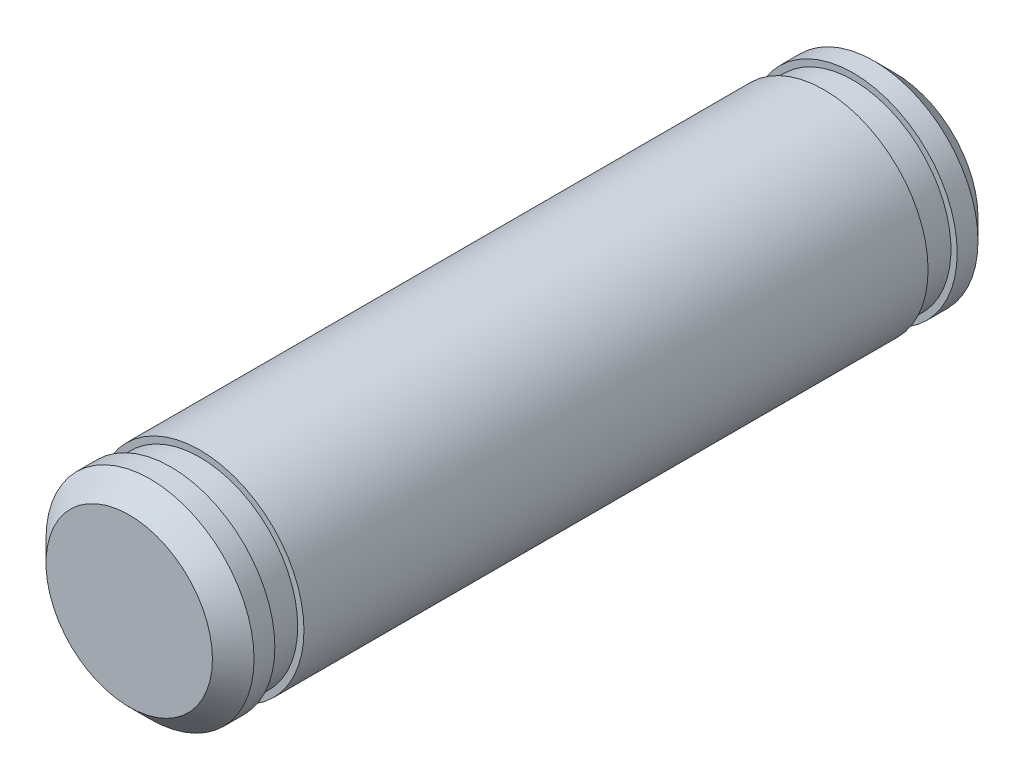
SolidWorks part; units mm, degrees
material "Chromowa stal nierdzewna"
ref_plane "Płaszczyzna przednia" through (0, 0, 0) normal (0, 0, 1) x (1, 0, 0)
ref_plane "Płaszczyzna górna" through (0, 0, 0) normal (0, 1, 0) x (1, 0, 0)
ref_plane "Płaszczyzna prawa" through (0, 0, 0) normal (1, 0, 0) x (0, 0, -1)
sketch "Szkic1" plane through (0, 0, 0) normal (0, 0, 1) x (1, 0, 0)
  circle A0 centre (0, 0) radius 2.5
  dimension "D1" = 5
extrude "Dodanie-wyciągnięcie1" add sketch "Szkic1" along normal blind 18.4
chamfer "Sfazowanie1" distance 0.5 angle 45 2 edges at (2.5, 0, 0) (2.5, 0, 18.4)
sketch "Szkic2" plane through (0, 0, 18.4) normal (0, 0, 1) x (1, 0, 0)
  circle A0 centre (0, 0) radius 2.5
  circle A1 centre (0, 0) radius 2.35
  dimension "D1" = 5
  dimension "D2" = 4.7
extrude "Wytnij-wyciągnięcie1" cut sketch "Szkic2" against normal blind 0.7 from offset 1 offset against normal yes
sketch "Szkic3" plane through (0, 0, 0) normal (0, 0, -1) x (-1, 0, 0)
  circle A0 centre (0, 0) radius 2.5
  circle A1 centre (0, 0) radius 2.35
  dimension "D1" = 5
  dimension "D2" = 4.7
extrude "Wytnij-wyciągnięcie2" cut sketch "Szkic3" against normal blind 0.7 from offset 1 offset against normal yes
